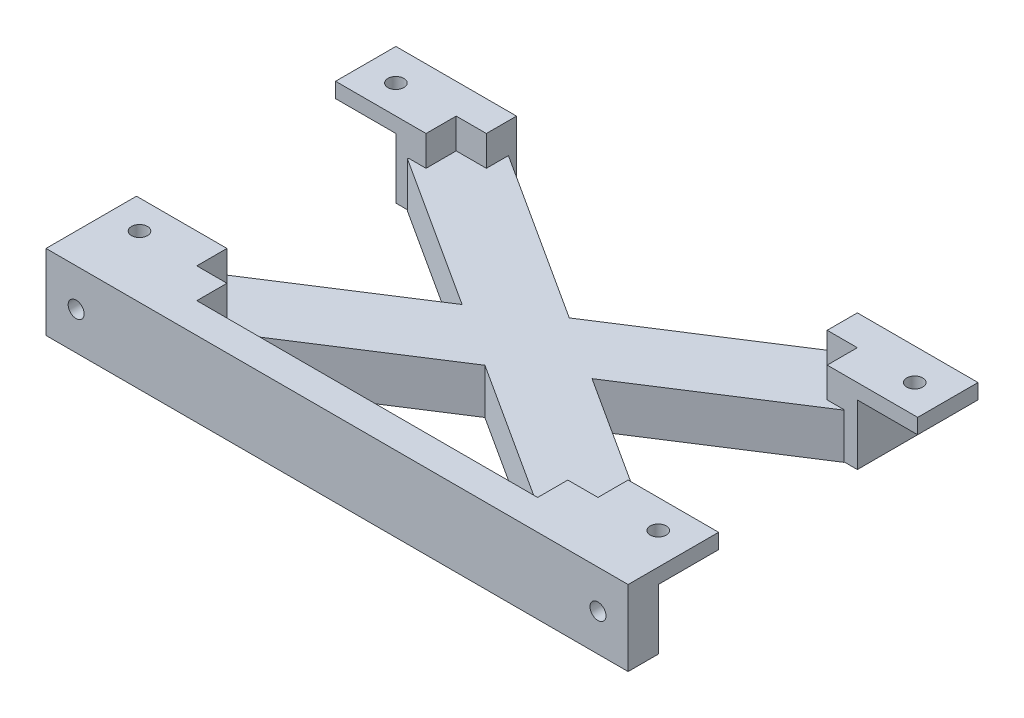
SolidWorks part; units mm, degrees
ref_plane "Front Plane" through (0, 0, 0) normal (0, 0, 1) x (1, 0, 0)
ref_plane "Top Plane" through (0, 0, 0) normal (0, 1, 0) x (1, 0, 0)
ref_plane "Right Plane" through (0, 0, 0) normal (1, 0, 0) x (0, 0, -1)
sketch "Sketch1" plane through (0, 0, 0) normal (0, 1, 0) x (1, 0, 0)
  line L0 (-66.5, 53) -> (-66.5, 33)
  line L1 (-66.5, -43) -> (66.5, -43) construction
  line L2 (-66.5, -43) -> (-66.5, 43) construction
  line L3 (-66.5, 43) -> (66.5, 43) construction
  line L4 (66.5, -43) -> (66.5, 43) construction
  line L5 (-66.5, -43) -> (66.5, 43) construction
  line L6 (-66.5, 43) -> (66.5, -43) construction
  line L7 (-76.5, 33) -> (-56.5, 33)
  line L8 (-76.5, 33) -> (-76.5, 53)
  line L9 (-76.5, 53) -> (-56.5, 53)
  line L10 (-56.5, 33) -> (-56.5, 53)
  line L11 (-76.5, 33) -> (-56.5, 53) construction
  line L12 (-76.5, 53) -> (-56.5, 33) construction
  line L13 (-76.5, 43) -> (-56.5, 43)
  line L14 (-66.5, -33) -> (-66.5, -53)
  line L15 (-76.5, -33) -> (-56.5, -33)
  line L16 (-76.5, -33) -> (-76.5, -53)
  line L17 (-76.5, -53) -> (-56.5, -53)
  line L18 (-56.5, -33) -> (-56.5, -53)
  line L19 (-76.5, -33) -> (-56.5, -53) construction
  line L20 (-76.5, -53) -> (-56.5, -33) construction
  line L21 (-76.5, -43) -> (-56.5, -43)
  line L22 (0, 0) -> (0, 43) construction
  line L23 (76.5, -43) -> (56.5, -43)
  line L24 (66.5, -33) -> (66.5, -53)
  line L25 (76.5, -53) -> (56.5, -53)
  line L26 (56.5, -33) -> (56.5, -53)
  line L27 (76.5, -33) -> (56.5, -33)
  line L28 (76.5, -33) -> (76.5, -53)
  line L29 (66.5, 53) -> (66.5, 33)
  line L30 (76.5, 43) -> (56.5, 43)
  line L31 (76.5, 53) -> (56.5, 53)
  line L32 (56.5, 33) -> (56.5, 53)
  line L33 (76.5, 33) -> (56.5, 33)
  line L34 (76.5, 33) -> (76.5, 53)
  point P0 (0, 0)
  dimension "D1" = 133
  dimension "D2" = 86
  dimension "D3" = 20
  dimension "D4" = 20
  dimension "D5" = 20
  dimension "D6" = 20
extrude "Boss-Extrude1" add sketch "Sketch1" along normal blind 10 contours L16 L21 L14 L15 | L21 L16 L17 L14 | L21 L14 L17 L18 | L13 L8 L7 L0 | L8 L13 L0 L9 | L0 L13 L10 L9 | L32 L30 L29 L31 | L30 L34 L31 L29 | L33 L34 L30 L29 | L23 L26 L25 L24 | L28 L23 L24 L25 | L28 L27 L24 L23 region at (-61.5, 0, -48) region at (-71.5, 0, -48) region at (-71.5, 0, -38) region at (-71.5, 0, 38) region at (-61.5, 0, 48) region at (-71.5, 0, 48) region at (71.5, 0, 48) region at (71.5, 0, 38) region at (61.5, 0, 48) region at (71.5, 0, -48) region at (61.5, 0, -48) region at (71.5, 0, -38)
extrude "Boss-Extrude2" add sketch "Sketch1<3>" against normal blind 15 contours L21 L16 L17 L14 | L14 L21 L18 L15 | L21 L14 L17 L18 | L16 L21 L14 L15 | L28 L23 L24 L25 | L28 L27 L24 L23 | L23 L26 L25 L24 | L24 L27 L26 L23 | L33 L34 L30 L29 | L30 L34 L31 L29 | L32 L30 L29 L31 | L33 L29 L30 L32 | L0 L13 L10 L9 | L13 L0 L7 L10 | L13 L8 L7 L0 | L8 L13 L0 L9 region at (-61.5, 0, -48) region at (-71.5, 0, -48) region at (-61.5, 0, -38) region at (-71.5, 0, -38) region at (-61.5, 0, 38) region at (-71.5, 0, 38) region at (-61.5, 0, 48) region at (-71.5, 0, 48) region at (71.5, 0, 48) region at (71.5, 0, 38) region at (61.5, 0, 48) region at (61.5, 0, 38) region at (71.5, 0, -48) region at (61.5, 0, -48) region at (71.5, 0, -38) region at (61.5, 0, -38)
sketch "Sketch1<3>" plane through (0, 0, 0) normal (0, 1, 0) x (1, 0, 0) same geometry as "Sketch1"
sketch "Sketch2" plane through (0, 0, 0) normal (0, 1, 0) x (1, 0, 0)
  line L0 (-72.3356, 32.6611) -> (59.6644, -52.3389)
  line L1 (-72.3356, 32.6611) -> (-59.6644, 52.3389)
  line L2 (59.6644, -52.3389) -> (72.3356, -32.6611)
  line L3 (-59.6644, 52.3389) -> (72.3356, -32.6611)
  line L4 (-72.3356, 32.6611) -> (72.3356, -32.6611) construction
  line L5 (59.6644, -52.3389) -> (-59.6644, 52.3389) construction
  line L6 (72.2153, 32.848) -> (-59.7847, -52.152)
  line L7 (72.2153, 32.848) -> (59.7847, 52.152)
  line L8 (-59.7847, -52.152) -> (-72.2153, -32.848)
  line L9 (59.7847, 52.152) -> (-72.2153, -32.848)
  line L10 (72.2153, 32.848) -> (-72.2153, -32.848) construction
  line L11 (-59.7847, -52.152) -> (59.7847, 52.152) construction
  point P1 (0, 0)
  point P2 (0, 0)
extrude "Boss-Extrude3" add sketch "Sketch2" against normal blind 15 contours L9 L3 L1 L0 | L3 L9 L0 L6 | L7 L9 L3 L6 | L3 L6 L0 L2 | L0 L9 L8 L6 region at (-38.0704, 0, -24.8896) region at (0, 0, 0) region at (-38.1809, 0, 24.948) region at (38.0704, 0, 24.8896) region at (38.1809, 0, -24.948)
sketch "Sketch3" plane through (-76.5, 0, 0) normal (-1, 0, 0) x (0, 0, 1)
  line L0 (-33, 10) -> (-33, -15) construction
  line L1 (-53, 10) -> (-33, 10)
  line L2 (-53, 10) -> (-53, 5)
  line L3 (-53, 5) -> (-33, 5)
  line L4 (-33, 10) -> (-33, 5)
  line L5 (53, 10) -> (53, -15) construction
  line L6 (33, 10) -> (53, 10)
  line L7 (33, 10) -> (33, 5)
  line L8 (33, 5) -> (53, 5)
  line L9 (53, 10) -> (53, 5)
  dimension "D1" = 5
extrude "Boss-Extrude4" add sketch "Sketch3" along normal blind 20
mirror "Mirror1" about plane through (0, 0, 0) normal (1, 0, 0) of "Boss-Extrude4"
hole_wizard "#4 (0.209) Diameter Hole1" positions "3DSketch1" profile "Sketch4" hole size "#4" standard "ANSI Inch" end condition through all
sketch3d "3DSketch1"
  line L1 (96.5, 10, -53) -> (56.5, 10, -53) construction
  line L2 (86.5, 10, -53) -> (86.5, 10, 53) construction
  line L3 (96.5, 10, 53) -> (56.5, 10, 53) construction
  line L5 (96.5, 10, -33) -> (96.5, 10, -53) construction
  line L6 (-86.5, 10, -53) -> (-86.5, 10, 53) construction
  line L7 (-96.5, 10, -53) -> (-56.5, 10, -53) construction
  line L8 (-96.5, 10, 53) -> (-56.5, 10, 53) construction
  line L10 (-96.5, 10, -33) -> (-96.5, 10, -53) construction
  line L11 (96.5, 10, -43) -> (-96.5, 10, -43) construction
  line L13 (96.5, 10, 43) -> (-96.5, 10, 43) construction
  line L14 (96.5, 10, 53) -> (96.5, 10, 33) construction
  line L15 (-96.5, 10, 53) -> (-96.5, 10, 33) construction
  point P0 (-86, 10, -42.5)
  point P2 (-86, 10, 42.5)
  point P4 (86, 10, -42.5)
  point P6 (86, 10, 42.5)
  dimension "D1" = 10
  dimension "D2" = 10
sketch "Sketch4" plane through (-86, 10, -42.5) normal (1, 0, 0) x (0, 0, 1)
  line L0 (0, 0) -> (0, 25)
  line L1 (0, 25) -> (2.6543, 25)
  line L2 (2.6543, 25) -> (2.6543, 0)
  line L5 (2.6543, 0) -> (0, 0)
  line L11 (0, -6.35) -> (0, 107.95) construction
  dimension "Thru Hole Dia." = 5.3086
  dimension "Thru Hole Depth" = 25
sketch "Sketch5" plane through (0, 0, 53) normal (0, 0, 1) x (1, 0, 0)
  line L0 (-96.5, 5) -> (-96.5, 10) construction
  line L1 (96.5, 10) -> (-96.5, 10)
  line L2 (96.5, 10) -> (96.5, -15)
  line L3 (96.5, -15) -> (-96.5, -15)
  line L4 (-96.5, 10) -> (-96.5, -15)
  line L5 (-76.5, -15) -> (-56.5, -15) construction
extrude "Boss-Extrude5" add sketch "Sketch5" along normal blind 10
hole_wizard "#4 (0.209) Diameter Hole2" positions "Sketch6" profile "Sketch7" hole size "#4" standard "ANSI Inch" end condition through all
sketch "Sketch6" plane through (0, 0, 53) normal (0, 0, -1) x (-1, 0, 0)
  line L0 (-96.5, -5) -> (-76.5, -5) construction
  line L1 (-96.5, -15) -> (-96.5, 5) construction
  line L2 (-76.5, 5) -> (-76.5, -15) construction
  line L4 (-86.5, 5) -> (-86.5, -15) construction
  line L5 (-96.5, 5) -> (-76.5, 5) construction
  line L6 (-76.5, -15) -> (-96.5, -15) construction
  line L8 (86.5, 5) -> (86.5, -10) construction
  line L9 (96.5, 5) -> (76.5, 5) construction
  line L11 (76.5, -5) -> (96.5, -5) construction
  line L12 (76.5, 5) -> (76.5, -15) construction
  line L13 (96.5, 5) -> (96.5, -15) construction
  point P0 (-86.5, -2.6748)
  point P2 (86.5, -2.5)
sketch "Sketch7" plane through (86.5, -2.6748, 53) normal (1, 0, 0) x (0, 1, 0)
  line L0 (0, 0) -> (0, 10)
  line L1 (0, 10) -> (2.6543, 10)
  line L2 (2.6543, 10) -> (2.6543, 0)
  line L5 (2.6543, 0) -> (0, 0)
  line L11 (0, -6.35) -> (0, 107.95) construction
  dimension "Thru Hole Dia." = 5.3086
  dimension "Thru Hole Depth" = 10
